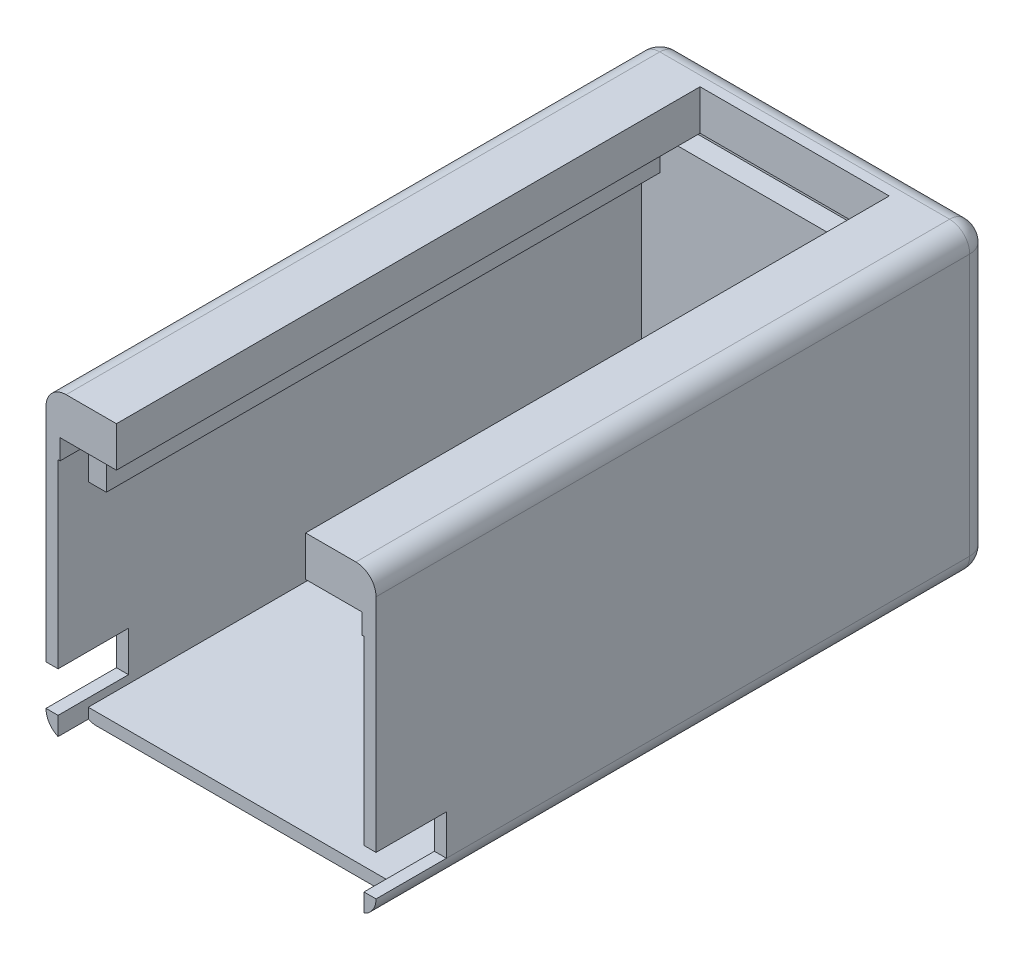
SolidWorks part; units mm, degrees
ref_plane "Front Plane" through (0, 0, 0) normal (0, 0, 1) x (1, 0, 0)
ref_plane "Top Plane" through (0, 0, 0) normal (0, 1, 0) x (1, 0, 0)
ref_plane "Right Plane" through (0, 0, 0) normal (1, 0, 0) x (0, 0, -1)
sketch "Croquis1" plane through (0, 0, 0) normal (0, 1, 0) x (1, 0, 0)
  line L4 (-41, 85) -> (41, 85)
  line L5 (41, 85) -> (41, -70)
  line L6 (41, -70) -> (-41, -70)
  line L7 (-41, -70) -> (-41, 85)
  line L9 (-33.5, 77.5) -> (33.5, 77.5)
  line L10 (-33.5, 77.5) -> (-33.5, -65)
  line L11 (-33.5, -65) -> (33.5, -65)
  line L12 (33.5, 77.5) -> (33.5, -65)
  dimension "D1" = 70
  dimension "D2" = 85
  dimension "D3" = 41
  dimension "D4" = 41
  dimension "D5" = 7.5
  dimension "D6" = 7.5
  dimension "D7" = 7.5
  dimension "D8" = 5
extrude "Saliente-Extruir1" add sketch "Croquis1" along normal blind 5 contours L12 L9 L10 L11 | L7 L6 L5 L4 L9 L12 L11 L10 region at (0, 0, -83.2465) region at (0, 0, -6.25)
extrude "Saliente-Extruir2" add sketch "Croquis1<3>" along normal blind 80
sketch "Croquis1<3>" plane through (0, 0, 0) normal (0, 1, 0) x (1, 0, 0) same geometry as "Croquis1"
sketch "Croquis2" plane through (-41, 0, 0) normal (-1, 0, 0) x (0, 0, 1)
  line L0 (70, 0) -> (-85, 0) construction
  line L1 (65, 5) -> (50, 5)
  line L2 (65, 5) -> (65, 15)
  line L3 (65, 15) -> (50, 15)
  line L4 (50, 5) -> (50, 15)
  line L5 (70, 80) -> (70, 0) construction
  line L6 (65, 15) -> (70, 15)
  line L7 (70, 15) -> (70, 5)
  line L8 (70, 5) -> (65, 5)
  line M6 (70, 0) -> (70, 80)
  dimension "D1" = 5
  dimension "D2" = 5
  dimension "D3" = 15
  dimension "D4" = 10
extrude "Cortar-Extruir1" cut sketch "Croquis2" against normal blind 120 contours L8 L6 L2 M6 | L4 L1 L2 L3 region at (-41, 10, 57.5) region at (-41, 10, 67.5)
sketch "Croquis4" plane through (0, 0, 70) normal (0, 0, 1) x (1, 0, 0)
  line L0 (-37.5, 59.5) -> (37.5, 59.5)
  line L7 (-37.5, 65) -> (-37.5, 59.5)
  line L8 (37.5, 59.5) -> (37.5, 65)
  line L9 (37.5, 65) -> (-37.5, 65)
  line L10 (-41, 80) -> (41, 80) construction
  line L11 (-41, 80) -> (-41, 15) construction
  line L12 (41, 80) -> (41, 15) construction
  dimension "D1" = 15
  dimension "D2" = 5.5
  dimension "D3" = 3.5
  dimension "D4" = 3.5
extrude "Cortar-Extruir2" cut sketch "Croquis4" against normal blind 152.5
sketch "Croquis5" plane through (0, 80, 0) normal (0, 1, 0) x (1, 0, 0)
  line L11 (33.5, -65) -> (33.5, -70)
  line L12 (-41, -70) -> (41, -70) construction
  line L13 (33.5, -70) -> (-33.5, -70)
  line L14 (-33.5, -70) -> (-33.5, -65)
  line L15 (-33.5, -65) -> (33.5, -65)
extrude "Cortar-Extruir4" cut sketch "Croquis5" against normal blind 140
sketch "Croquis6" plane through (-33.5, 0, 0) normal (1, 0, 0) x (0, 0, -1)
  line L0 (-70, 65) -> (-70, 80)
  line L1 (-70, 80) -> (77.5, 80)
  line L2 (77.5, 80) -> (77.5, 65)
  line L3 (77.5, 65) -> (-70, 65)
extrude "Saliente-Extruir3" add sketch "Croquis6" along normal blind 10
mirror "Simetría1" about plane through (0, 0, 0) normal (1, 0, 0) of "Saliente-Extruir3"
sketch "Croquis7" plane through (0, 0, 70) normal (0, 0, 1) x (1, 0, 0)
  line L7 (-33.5, 51.5) -> (-38, 51.5)
  line L8 (-33.5, 15) -> (-33.5, 59.5) construction
  line L9 (-38, 51.5) -> (-38, 3)
  line L10 (-38, 3) -> (38, 3)
  line L11 (38, 3) -> (38, 51.5)
  line L12 (38, 51.5) -> (-33.5, 51.5)
  line L13 (-41, 80) -> (41, 80)
  line L14 (41, 80) -> (41, 75)
  line L15 (41, 80) -> (41, 15) construction
  line L16 (41, 75) -> (-41, 75)
  line L17 (-41, 80) -> (-41, 15) construction
  line L18 (-41, 75) -> (-41, 80)
  line L19 (-37.5, 59.5) -> (-33.5, 59.5) construction
  line L20 (-33.5, 0) -> (-41, 0) construction
  line M6 (-23.5, 65) -> (-23.5, 80)
  line M7 (-23.5, 80) -> (-41, 80)
  line M8 (-41, 80) -> (-41, 15)
  line M10 (-33.5, 15) -> (-33.5, 59.5)
  dimension "D1" = 8
  dimension "D2" = 4.5
  dimension "D3" = 3
  dimension "D4" = 3
  dimension "D5" = 5
extrude "Cortar-Extruir5" cut sketch "Croquis7" against normal blind 147.5 contours L11 L12 L10 M10 | L9 L10 L7 M10 region at (0, 27.25, 70)
extrude "Cortar-Extruir6" cut sketch "Croquis7<3>" against normal blind 167.5 contours L16 M6 M7 M8 | L16 L14 L13 M6 region at (-32.25, 77.5, 70) region at (8.75, 77.5, 70)
sketch "Croquis7<3>" plane through (0, 0, 70) normal (0, 0, 1) x (1, 0, 0) same geometry as "Croquis7"
sketch "Croquis8" plane through (0, 0, 0) normal (0, -1, 0) x (-1, 0, 0)
  line L0 (-41, -70) -> (-33.5, -70) construction
  line L1 (-38, -70) -> (38, -70)
  line L2 (-38, -70) -> (-38, -60)
  line L3 (-38, -60) -> (38, -60)
  line L4 (38, -70) -> (38, -60)
  line L5 (-41, 85) -> (-41, -70) construction
  line L6 (41, -70) -> (41, 85) construction
  dimension "D1" = 10
  dimension "D2" = 3
  dimension "D3" = 3
extrude "Cortar-Extruir7" cut sketch "Croquis8" against normal blind 60
sketch "Croquis9" plane through (0, 0, 0) normal (0, -1, 0) x (1, 0, 0)
  line L0 (-41, 70) -> (-41, -85) construction
  line L1 (-41, 67.5) -> (41, 67.5)
  line L2 (-41, 67.5) -> (-41, 70)
  line L3 (-41, 70) -> (41, 70)
  line L4 (41, 67.5) -> (41, 70)
  dimension "D1" = 2.5
extrude "Cortar-Extruir8" cut sketch "Croquis9" against normal blind 300
fillet "Redondeo1" radius 5 8 edges at (0, 75, -85) (41, 75, -8.75) (-41, 75, -8.75) (-41, 0, -8.75) (41, 0, -8.75) (0, 0, -85) (-41, 37.5, -85) (41, 37.5, -85)
